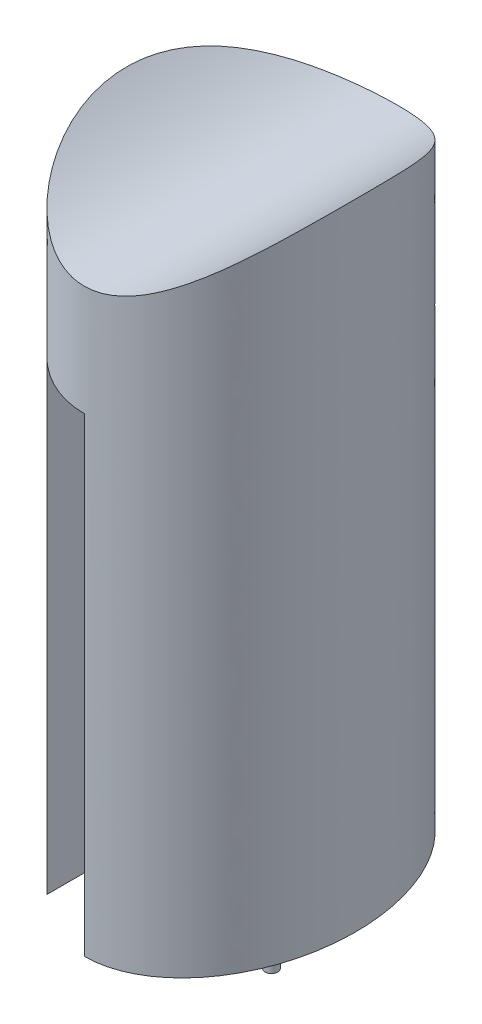
SolidWorks part; units mm, degrees
ref_plane "Front Plane" through (0, 0, 0) normal (0, 0, 1) x (1, 0, 0)
ref_plane "Top Plane" through (0, 0, 0) normal (0, 1, 0) x (1, 0, 0)
ref_plane "Right Plane" through (0, 0, 0) normal (1, 0, 0) x (0, 0, -1)
sketch "Sketch2" plane through (0, 0, 0) normal (0, 1, 0) x (1, 0, 0)
  line L0 (0, -100) -> (0, -130) construction
  line L1 (-60, -38.4615) -> (-60, -100.7905) construction
  ellipse E0 centre (0, 0) end of major axis (0, 130) minor radius 95
  ellipse E1 centre (0, 0) end of major axis (0, 100) minor radius 65
  dimension "D1" = 260
  dimension "D2" = 190
  dimension "D3" = 30
  dimension "D4" = 30
  dimension "D5" = 100
  dimension "D6" = 60
extrude "Boss-Extrude2" add sketch "Sketch2" along normal mid plane 480
sketch "Sketch4" plane through (0, -240, 0) normal (0, -1, 0) x (1, 0, 0)
  line L0 (0, 100) -> (0, 130) construction
  line L1 (-60, 38.4615) -> (-60, 100.7905) construction
  line L2 (0, 100) -> (0, 130)
  line L3 (-60, 38.4615) -> (-60, 100.7905)
  ellipse E0 centre (0, 0) end of major axis (0, -130) minor radius 95 (-60, 100.7905) -> (0, 130) ccw construction
  ellipse E1 centre (0, 0) end of major axis (0, -100) minor radius 65
  ellipse E2 centre (0, 0) end of major axis (0, -100) minor radius 65 (0, 100) -> (-60, 38.4615) ccw
  ellipse E3 centre (0, 0) end of major axis (0, -130) minor radius 95
  ellipse E4 centre (0, 0) end of major axis (0, -130) minor radius 95 (0, 130) -> (-60, 100.7905) ccw
  ellipse E5 centre (0, 0) end of major axis (0, -100) minor radius 65 (-60, 38.4615) -> (0, 100) ccw construction
  dimension "D1" = 0
  dimension "D2" = 0
extrude "Cut-Extrude1" cut sketch "Sketch4" against normal blind 390
sketch "Sketch5" plane through (0, 0, 0) normal (0, 0, 1) x (1, 0, 0)
  line L0 (95, 286.625) -> (95, 240)
  line L1 (95, 240) -> (-95, 240)
  line L2 (-95, 240) -> (-95, 286.625)
  spline S0 degree 2 poles (-110.0834, 302.0918) (0, 180.9082) (110.0834, 302.0918) knots 0 0 0 1 1 1 construction
  spline S1 degree 2 poles (-95, 286.625) (0, 196.375) (95, 286.625) knots 0.068509 0.068509 0.068509 0.931491 0.931491 0.931491
extrude "Boss-Extrude3" add sketch "Sketch5" along normal mid plane 260 contours S1 L0 L1 L2
sketch "Sketch6" plane through (0, -240, 0) normal (0, -1, 0) x (1, 0, 0)
  line L1 (225.729, -255.2298) -> (-261.1087, -255.2298)
  line L2 (225.729, -255.2298) -> (225.729, 322.6028)
  line L3 (225.729, 322.6028) -> (-261.1087, 322.6028)
  line L4 (-261.1087, -255.2298) -> (-261.1087, 322.6028)
  ellipse E0 centre (0, 0) end of major axis (0, -130) minor radius 95 (-95, 0) -> (0, -130) ccw construction
  ellipse E1 centre (0, 0) end of major axis (0, -130) minor radius 95 (0, -130) -> (95, 0) ccw construction
  ellipse E2 centre (0, 0) end of major axis (0, -130) minor radius 95 (95, 0) -> (0, 130) ccw construction
  ellipse E3 centre (0, 0) end of major axis (0, -130) minor radius 95 (0, 130) -> (-95, 0) ccw construction
  ellipse E4 centre (0, 0) end of major axis (0, -130) minor radius 95 (-95, 0) -> (0, -130) ccw
  ellipse E5 centre (0, 0) end of major axis (0, -130) minor radius 95 (0, -130) -> (95, 0) ccw
  ellipse E6 centre (0, 0) end of major axis (0, -130) minor radius 95 (95, 0) -> (0, 130) ccw
  ellipse E7 centre (0, 0) end of major axis (0, -130) minor radius 95 (0, 130) -> (-95, 0) ccw
extrude "Cut-Extrude4" cut sketch "Sketch6" against normal through all both and the other way through all
sketch "Sketch7" plane through (0, 240, 0) normal (0, -1, 0) x (1, 0, 0)
  line L0 (0, 100) -> (0, 130) construction
  line L1 (50.5, 25.25) -> (0, 25.25) construction
  line L2 (50.5, 25.25) -> (50.5, -25.25) construction
  line L3 (50.5, -25.25) -> (0, -25.25) construction
  line L4 (0, 25.25) -> (0, -25.25) construction
  line L5 (50.5, 25.25) -> (0, -25.25) construction
  line L6 (50.5, -25.25) -> (0, 25.25) construction
  line L7 (5.25, 14.75) -> (5.25, -14.75)
  line L8 (10.5, -20) -> (40, -20)
  line L9 (45.25, -14.75) -> (45.25, 14.75)
  line L10 (40, 20) -> (10.5, 20)
  arc A0 (10.5, 20) -> (5.25, 14.75) centre (5.25, 20) ccw
  arc A1 (45.25, 14.75) -> (40, 20) centre (45.25, 20) ccw
  arc A2 (40, -20) -> (45.25, -14.75) centre (45.25, -20) ccw
  arc A3 (5.25, -14.75) -> (10.5, -20) centre (5.25, -20) ccw
  arc A4 (8.9623, 16.2877) -> (10.5, 20) centre (5.25, 20) ccw construction
  arc A5 (5.25, 14.75) -> (8.9623, 16.2877) centre (5.25, 20) ccw construction
  arc A6 (8.9623, -16.2877) -> (5.25, -14.75) centre (5.25, -20) ccw construction
  arc A7 (10.5, -20) -> (8.9623, -16.2877) centre (5.25, -20) ccw construction
  arc A8 (45.25, -14.75) -> (41.5377, -16.2877) centre (45.25, -20) ccw construction
  arc A9 (41.5377, -16.2877) -> (40, -20) centre (45.25, -20) ccw construction
  arc A10 (41.5377, 16.2877) -> (45.25, 14.75) centre (45.25, 20) ccw construction
  arc A11 (40, 20) -> (41.5377, 16.2877) centre (45.25, 20) ccw construction
  point P0 (25.25, 0)
  dimension "D2" = 10.5
  dimension "D1" = 50.5
extrude "Boss-Extrude4" add sketch "Sketch7" along normal blind 521
ref_axis "axis robot spins on" through (25.25, 240, 0) along (0, -1, 0)
equation "\"∩╗┐cas_w\" = 38.1mm"
equation "\"cas_l\" = 83.0mm"
equation "\"cas_h\" = 280.0mm"
equation "\"rail_w\" = 50.5mm"
equation "\"rail_c\" = 10.5mm"
equation "\"D1@Sketch7\"=\"rail_w\""
equation "\"D2@Sketch7\"=\"rail_c\""
